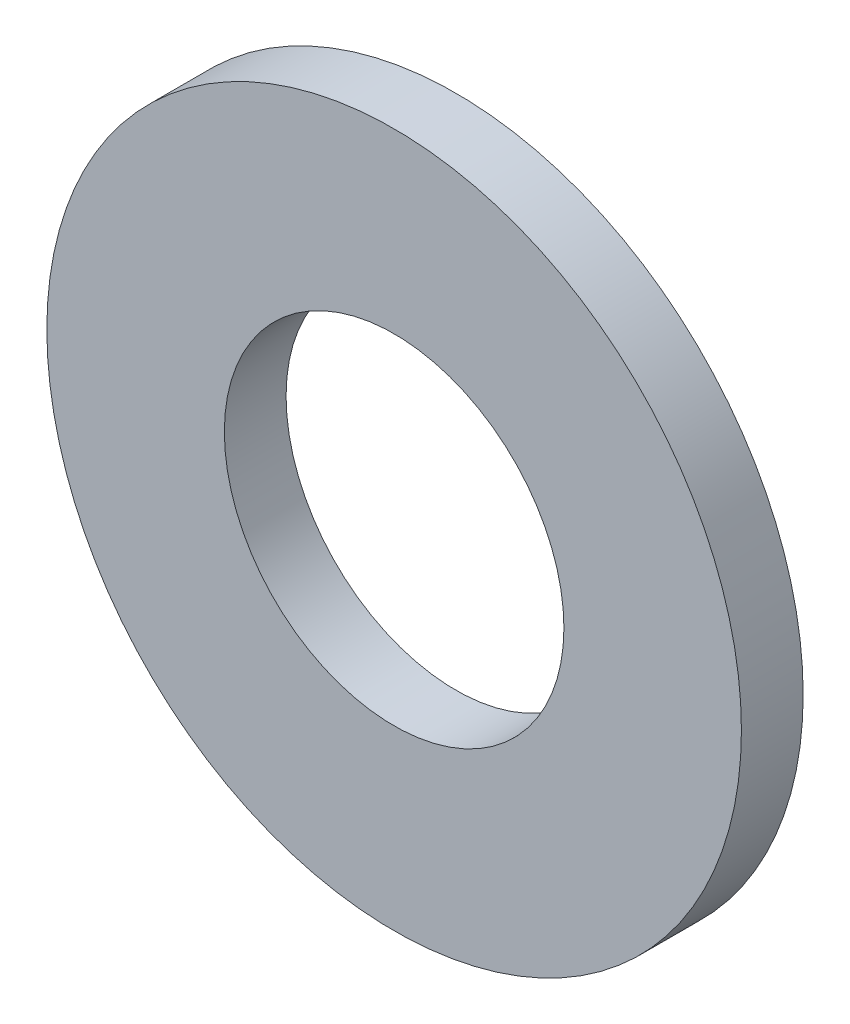
SolidWorks part; units mm, degrees
ref_plane "Front Plane" through (0, 0, 0) normal (0, 0, 1) x (1, 0, 0)
ref_plane "Top Plane" through (0, 0, 0) normal (0, 1, 0) x (1, 0, 0)
ref_plane "Right Plane" through (0, 0, 0) normal (1, 0, 0) x (0, 0, -1)
sketch "Sketch1" plane through (0, 0, 0) normal (0, 0, 1) x (1, 0, 0)
  circle A0 centre (0, 0) radius 2.25
  circle A1 centre (0, 0) radius 1.1
  dimension "OD" = 4.5
  dimension "ID1" = 2.2
extrude "Boss-Extrude1" add sketch "Sketch1" along normal blind 0.4
ref_axis "Center Axis 1" through (0, 0, 0.4) along (0, 0, -1)
ref_plane "Contact Plane 1" through (0, 0, 0.4) normal (0, 0, 1) x (1, 0, 0)
ref_plane "Contact Plane 2" through (0, 0, 0) normal (0, 0, -1) x (-1, 0, 0)
